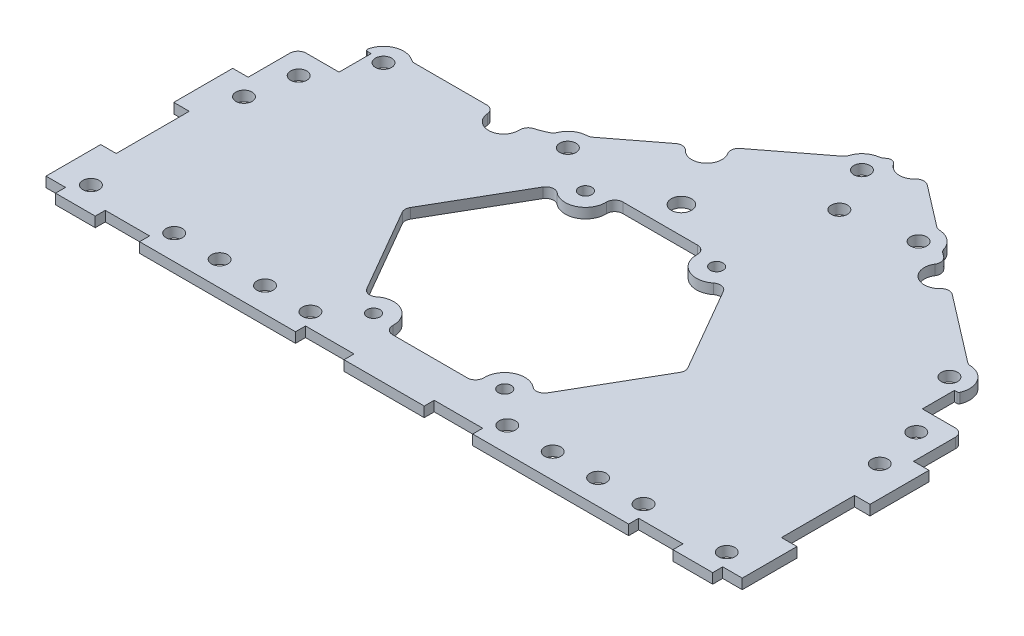
SolidWorks part; units mm, degrees
material "Alum Plate"
ref_plane "Front Plane" through (0, 0, 0) normal (0, 0, 1) x (1, 0, 0)
ref_plane "Top Plane" through (0, 0, 0) normal (0, 1, 0) x (1, 0, 0)
ref_plane "Right Plane" through (0, 0, 0) normal (1, 0, 0) x (0, 0, -1)
sketch "Top Layout" plane through (0, 0, 0) normal (0, 1, 0) x (1, 0, 0)
  line L0 (-114.046, -123.825) -> (-104.775, -123.825) construction
  line L1 (-104.775, -142.875) -> (-101.6, -142.875)
  line L2 (-104.775, -142.875) -> (-104.775, -104.775)
  line L3 (-104.775, -104.775) -> (-101.6, -104.775)
  line L4 (-101.6, -142.875) -> (-101.6, -104.775)
  line L5 (-104.775, -142.875) -> (-101.6, -104.775) construction
  line L6 (-104.775, -104.775) -> (-101.6, -142.875) construction
  line L7 (-19.05, -105.8164) -> (-101.6, -105.8164)
  line L8 (-19.05, -105.8164) -> (-19.05, -141.8336)
  line L9 (-19.05, -141.8336) -> (-101.6, -141.8336)
  line L10 (-101.6, -105.8164) -> (-101.6, -141.8336)
  line L11 (-19.05, -105.8164) -> (-101.6, -141.8336) construction
  line L12 (-19.05, -141.8336) -> (-101.6, -105.8164) construction
  line L13 (-133.096, -85.725) -> (-114.046, -85.725)
  line L14 (-133.096, -85.725) -> (-133.096, -161.925)
  line L15 (-133.096, -161.925) -> (-114.046, -161.925)
  line L16 (-114.046, -85.725) -> (-114.046, -161.925)
  line L17 (-133.096, -85.725) -> (-114.046, -161.925) construction
  line L18 (-133.096, -161.925) -> (-114.046, -85.725) construction
  line L19 (-104.775, -123.825) -> (0, -123.825) construction
  line L20 (0, -123.825) -> (0, 0) construction
  line L21 (-52.3528, -40.1717) -> (0, 0) construction
  line L22 (-70.6449, -16.3328) -> (-18.2922, 23.8388)
  line L23 (-34.0606, -64.0105) -> (18.2922, -23.8388)
  line L24 (-30.9251, 40.3023) -> (-122.2248, -29.7544)
  line L25 (-153.9748, -53.975) -> (-153.9748, -123.825)
  line L26 (-109.5248, -162.052) -> (109.5248, -162.052)
  line L27 (0, -162.052) -> (0, -123.825) construction
  line L28 (-109.5248, -162.052) -> (-109.5248, -20.0093) construction
  line L29 (-104.775, -142.875) -> (-104.775, -152.527)
  line L30 (-104.775, -152.527) -> (104.775, -152.527)
  line L31 (104.775, -104.775) -> (101.6, -104.775)
  line L32 (-144.4498, -73.025) -> (-109.5248, -73.025)
  line L33 (-144.4498, -73.025) -> (-144.4498, -123.825)
  line L34 (-144.4498, -123.825) -> (-109.5248, -123.825) construction
  line L35 (-109.5248, -73.025) -> (-109.5248, -162.052)
  line L36 (-144.4498, -73.025) -> (-109.5248, -123.825) construction
  line L37 (-144.4498, -123.825) -> (-109.5248, -73.025) construction
  line L38 (101.6, -142.875) -> (101.6, -104.775)
  line L39 (104.775, -142.875) -> (101.6, -142.875)
  line L40 (104.775, -142.875) -> (104.775, -104.775)
  line L41 (104.775, -142.875) -> (104.775, -152.527)
  line L42 (109.5248, -162.052) -> (109.5248, -20.0093) construction
  line L43 (30.9251, 40.3023) -> (122.2248, -29.7544)
  line L45 (19.05, -141.8336) -> (101.6, -141.8336)
  line L46 (101.6, -105.8164) -> (101.6, -141.8336)
  line L47 (19.05, -105.8164) -> (101.6, -105.8164)
  line L48 (19.05, -105.8164) -> (19.05, -141.8336)
  line L49 (133.096, -161.925) -> (114.046, -161.925)
  line L50 (114.046, -85.725) -> (114.046, -161.925)
  line L51 (133.096, -85.725) -> (114.046, -85.725)
  line L52 (133.096, -85.725) -> (133.096, -161.925)
  line L53 (144.4498, -123.825) -> (109.5248, -123.825) construction
  line L54 (109.5248, -73.025) -> (109.5248, -162.052)
  line L55 (144.4498, -73.025) -> (109.5248, -73.025)
  line L56 (144.4498, -73.025) -> (144.4498, -123.825)
  line L57 (-109.5248, -123.825) -> (-109.5248, -162.052) construction
  line L62 (-153.9748, -53.975) -> (-122.2248, -53.975)
  line L63 (-122.2248, -53.975) -> (-122.2248, -29.7544)
  line L64 (-144.4498, -123.825) -> (-153.9748, -123.825)
  line L65 (153.9748, -53.975) -> (153.9748, -123.825)
  line L66 (109.5248, -123.825) -> (109.5248, -162.052) construction
  line L67 (144.4498, -123.825) -> (153.9748, -123.825)
  line L68 (122.2248, -29.7544) -> (122.2248, -53.975)
  line L73 (-104.775, -104.775) -> (-104.775, -16.3647) construction
  line L74 (-95.25, -162.052) -> (-95.25, -9.0559) construction
  line L75 (-109.5248, -162.052) -> (-109.5248, -123.825) construction
  line L76 (109.5248, -162.052) -> (109.5248, -123.825) construction
  line L77 (122.2248, -53.975) -> (153.9748, -53.975)
  line L83 (104.775, -155.5496) -> (-104.775, -155.5496) construction
  line L88 (95.25, -162.052) -> (95.25, -9.0559) construction
  line L89 (104.775, -104.775) -> (104.775, -16.3647) construction
  line L92 (-104.775, -152.527) -> (-104.775, -162.052) construction
  line L93 (-14.605, -76.327) -> (14.605, -76.327)
  line L94 (-14.605, -76.327) -> (-14.605, -152.527)
  line L95 (-14.605, -152.527) -> (14.605, -152.527)
  line L96 (14.605, -76.327) -> (14.605, -152.527)
  line L97 (-14.605, -76.327) -> (14.605, -152.527) construction
  line L98 (-14.605, -152.527) -> (14.605, -76.327) construction
  line L99 (104.775, -152.527) -> (104.775, -162.052) construction
  line L100 (-19.05, -105.8164) -> (0, -105.8164) construction
  line L107 (0, -105.8164) -> (19.05, -105.8164) construction
  line L108 (104.775, -123.825) -> (114.046, -123.825) construction
  circle A0 centre (0, 0) radius 114.3
  circle A1 centre (0, 0) radius 6.35
  circle A2 centre (-52.3528, -40.1717) radius 17.8
  circle A3 centre (0, 0) radius 30.0482
  circle A4 centre (-52.3528, -40.1717) radius 30.0482
  arc A5 (-30.9251, 40.3023) -> (30.9251, 40.3023) centre (0, 0) cw
  point P2 (-103.1875, -123.825)
  point P7 (-60.325, -123.825)
  point P12 (-123.571, -123.825)
  point P30 (-126.9873, -98.425)
  point P35 (0, -114.427)
  point P53 (0, -152.527)
  dimension "D1" = 35.6
  dimension "D2" = 12.7
  dimension "D3" = 228.6
  dimension "D11" = 60.0964
  dimension "D12" = 50.8
  dimension "D14" = 52.5
  dimension "D4" = 3.175
  dimension "D5" = 19.05
  dimension "D6" = 76.2
  dimension "D7" = 82.55
  dimension "D8" = 38.1
  dimension "D9" = 104.775
  dimension "D10" = 18.0086
  dimension "D13" = 9.525
  dimension "D15" = 4.7498
  dimension "D16" = 9.525
  dimension "D17" = 9.652
  dimension "D18" = 50.8
  dimension "D19" = 12.446
  dimension "D20" = 65.9892
  dimension "D21" = 19.05
  dimension "D22" = 34.925
  dimension "D23" = 123.825
  dimension "D24" = 12.7
  dimension "D25" = 9.525
  dimension "D26" = 29.21
  dimension "D27" = 76.2
  dimension "D28" = 3.0226
sketch "Side Layout" plane through (0, 0, 0) normal (1, 0, 0) x (0, 0, -1)
  line L0 (0, -38.1) -> (0, 33.7344) construction
  line L1 (-114.3, -20.955) -> (114.3, -20.955)
  line L2 (-114.3, -20.955) -> (-114.3, -33.655)
  line L3 (-114.3, -33.655) -> (114.3, -33.655)
  line L4 (114.3, -20.955) -> (114.3, -33.655)
  line L5 (-114.3, -20.955) -> (114.3, -33.655) construction
  line L6 (-114.3, -33.655) -> (114.3, -20.955) construction
  line L7 (-9.525, -32.9406) -> (9.525, -32.9406)
  line L8 (-9.525, -32.9406) -> (-9.525, -38.1)
  line L9 (-9.525, -38.1) -> (9.525, -38.1)
  line L10 (9.525, -32.9406) -> (9.525, -38.1)
  line L11 (-9.525, -32.9406) -> (9.525, -38.1) construction
  line L12 (-9.525, -38.1) -> (9.525, -32.9406) construction
  line L13 (-11.9126, -29.3338) -> (11.9126, -29.3338)
  line L14 (-11.9126, -29.3338) -> (-11.9126, -32.9406)
  line L15 (-11.9126, -32.9406) -> (11.9126, -32.9406)
  line L16 (11.9126, -29.3338) -> (11.9126, -32.9406)
  line L17 (-11.9126, -29.3338) -> (11.9126, -32.9406) construction
  line L18 (-11.9126, -32.9406) -> (11.9126, -29.3338) construction
  line L19 (-6.35, -32.9406) -> (6.35, -32.9406)
  line L20 (-6.35, -32.9406) -> (-6.35, 33.7344)
  line L21 (-6.35, 33.7344) -> (6.35, 33.7344)
  line L22 (6.35, -32.9406) -> (6.35, 33.7344)
  line L23 (-6.35, -32.9406) -> (6.35, 33.7344) construction
  line L24 (-6.35, 33.7344) -> (6.35, -32.9406) construction
  line L25 (-162.052, 0) -> (-123.825, 0) construction
  line L26 (114.3, -33.655) -> (114.3, 0) construction
  line L27 (-142.875, 19.05) -> (-104.775, 19.05)
  line L28 (-40.1717, -9.525) -> (-40.1717, 5.4) construction
  line L29 (-142.875, 19.05) -> (-142.875, -19.05)
  line L30 (-142.875, -19.05) -> (-104.775, -19.05)
  line L31 (-104.775, 19.05) -> (-104.775, -19.05)
  line L32 (-142.875, 19.05) -> (-104.775, -19.05) construction
  line L33 (-142.875, -19.05) -> (-104.775, 19.05) construction
  line L34 (-130.175, -38.1) -> (-117.9516, -38.1) construction
  line L35 (-57.9717, -14.6) -> (-22.3717, -14.6)
  line L36 (-30.0482, -2.794) -> (30.0482, -2.794)
  line L37 (-30.0482, -2.794) -> (-30.0482, -20.955)
  line L38 (-30.0482, -20.955) -> (30.0482, -20.955)
  line L39 (30.0482, -2.794) -> (30.0482, -20.955)
  line L40 (-30.0482, -2.794) -> (30.0482, -20.955) construction
  line L41 (-30.0482, -20.955) -> (30.0482, -2.794) construction
  line L42 (-30.0482, -2.794) -> (-30.0482, 0) construction
  line L43 (-123.825, 0) -> (0, 0) construction
  line L44 (-57.9717, -14.6) -> (-57.9717, 25.4)
  line L45 (-57.9717, 25.4) -> (-22.3717, 25.4)
  line L46 (-22.3717, -14.6) -> (-22.3717, 25.4)
  line L47 (-19.05, 0) -> (19.05, 0)
  line L48 (-19.05, 0) -> (-19.05, -1.9812)
  line L49 (-19.05, -1.9812) -> (19.05, -1.9812)
  line L50 (19.05, 0) -> (19.05, -1.9812)
  line L51 (-19.05, 0) -> (19.05, -1.9812) construction
  line L52 (-19.05, -1.9812) -> (19.05, 0) construction
  line L53 (-70.2199, -3.175) -> (-10.1235, -3.175)
  line L54 (-70.2199, -3.175) -> (-70.2199, -15.875)
  line L55 (-70.2199, -15.875) -> (-10.1235, -15.875)
  line L56 (-10.1235, -3.175) -> (-10.1235, -15.875)
  line L57 (-70.2199, -3.175) -> (-10.1235, -15.875) construction
  line L58 (-70.2199, -15.875) -> (-10.1235, -3.175) construction
  line L59 (-40.1717, -9.525) -> (-40.1717, 0) construction
  line L60 (-57.9717, -14.6) -> (-22.3717, 25.4) construction
  line L61 (-57.9717, 25.4) -> (-22.3717, -14.6) construction
  line L62 (-22.3717, 0) -> (-57.9717, 0) construction
  line L63 (-137.8162, 0) -> (-123.825, -13.9912) construction
  line L64 (-139.065, 15.24) -> (-108.585, 15.24) construction
  line L65 (-139.065, 15.24) -> (-139.065, -15.24) construction
  line L66 (-139.065, -15.24) -> (-108.585, -15.24) construction
  line L67 (-108.585, 15.24) -> (-108.585, -15.24) construction
  line L68 (-139.065, 15.24) -> (-108.585, -15.24) construction
  line L69 (-139.065, -15.24) -> (-108.585, 15.24) construction
  line L70 (-137.8162, 0) -> (-123.825, 13.9912) construction
  line L71 (-123.825, -13.9912) -> (-109.8338, 0) construction
  line L72 (-123.825, 13.9912) -> (-109.8338, 0) construction
  line L73 (-137.8162, 0) -> (-109.8338, 0) construction
  line L74 (-123.825, -13.9912) -> (-123.825, 13.9912) construction
  line L75 (-6.35, 17.8594) -> (6.35, 17.8594)
  line L76 (114.3, 0) -> (-114.3, 0) construction
  line L77 (-22.3717, 19.05) -> (-6.35, 19.05) construction
  line L78 (-123.825, 38.1) -> (-97.9206, 38.1) construction
  line L79 (-19.05, -3.5814) -> (19.05, -3.5814)
  line L80 (-19.05, -3.5814) -> (-19.05, -1.9812)
  line L81 (-19.05, -1.9812) -> (19.05, -1.9812)
  line L82 (19.05, -3.5814) -> (19.05, -1.9812)
  line L83 (-19.05, -3.5814) -> (19.05, -1.9812) construction
  line L84 (-19.05, -1.9812) -> (19.05, -3.5814) construction
  line L85 (-8.7376, -16.7608) -> (8.7376, -16.7608)
  line L86 (-8.7376, -16.7608) -> (-8.7376, -29.3338)
  line L87 (-8.7376, -29.3338) -> (8.7376, -29.3338)
  line L88 (8.7376, -16.7608) -> (8.7376, -29.3338)
  line L89 (-8.7376, -16.7608) -> (8.7376, -29.3338) construction
  line L90 (-8.7376, -29.3338) -> (8.7376, -16.7608) construction
  line L91 (-8.7376, -3.5814) -> (8.7376, -3.5814)
  line L92 (-8.7376, -3.5814) -> (-8.7376, -16.1544)
  line L93 (-8.7376, -16.1544) -> (8.7376, -16.1544)
  line L94 (8.7376, -3.5814) -> (8.7376, -16.1544)
  line L95 (-8.7376, -3.5814) -> (8.7376, -16.1544) construction
  line L96 (-8.7376, -16.1544) -> (8.7376, -3.5814) construction
  circle A0 centre (-123.825, 0) radius 18.0086
  circle A1 centre (-123.825, 0) radius 38.1
  circle A2 centre (-139.065, 15.24) radius 1.905
  circle A3 centre (-108.585, 15.24) radius 1.905
  circle A4 centre (-108.585, -15.24) radius 1.905
  circle A5 centre (-139.065, -15.24) radius 1.905
  circle A6 centre (-137.8162, 0) radius 1.6002
  circle A7 centre (-123.825, 13.9912) radius 1.6002
  circle A8 centre (-109.8338, 0) radius 1.6002
  circle A9 centre (-123.825, -13.9912) radius 1.6002
  point P0 (0, -27.305)
  point P6 (0, -31.1372)
  point P7 (0, -35.5203)
  point P21 (0, 0.3969)
  point P32 (0, -11.8745)
  point P43 (0, -0.9906)
  point P55 (-40.1717, -9.525)
  point P72 (-40.1717, 5.4)
  point P88 (0, -23.0473)
  point P93 (0, -2.7813)
  point P102 (0, -9.8679)
  dimension "D17" = 3.81
  dimension "D18" = 3.2004
  dimension "D1" = 12.7
  dimension "D2" = 5.1594
  dimension "D3" = 19.05
  dimension "D4" = 3.6068
  dimension "D5" = 23.8252
  dimension "D6" = 12.7
  dimension "D7" = 18.161
  dimension "D8" = 1.9812
  dimension "D9" = 12.7
  dimension "D10" = 40
  dimension "D11" = 25.4
  dimension "D12" = 50.8
  dimension "D13" = 41.275
  dimension "D14" = 30.48
  dimension "D15" = 4.445
  dimension "D16" = 19.7866
  dimension "D19" = 15.875
  dimension "D20" = 6.35
  dimension "D21" = 38.1
  dimension "D22" = 1.6002
  dimension "D23" = 38.1
  dimension "D24" = 17.4752
  dimension "D25" = 12.573
ref_plane "Plane1" through (0, 25.4, 0) normal (0, 1, 0) x (1, 0, 0)
sketch "Sketch3" plane through (0, 25.4, 0) normal (0, 1, 0) x (1, 0, 0)
  line L0 (-104.775, -36.3747) -> (-30.9251, 20.2924)
  line L1 (-104.775, -104.775) -> (-104.775, -16.3647) construction
  line L2 (0, -200130.175) -> (0, 199882.0484) construction
  line L3 (-30.9251, 40.3023) -> (-122.2248, -29.7544) construction
  line L5 (-104.775, -36.3747) -> (-104.775, -77.6497)
  line L6 (-92.075, -77.6497) -> (-104.775, -77.6497)
  line L7 (30.9251, 20.2924) -> (104.775, -36.3747)
  line L8 (104.775, -77.6497) -> (92.075, -77.6497)
  line L9 (104.775, -36.3747) -> (104.775, -77.6497)
  line L11 (104.775, -104.775) -> (104.775, -16.3647) construction
  line L12 (30.9251, 40.3023) -> (122.2248, -29.7544) construction
  line L13 (92.075, -74.6536) -> (24.1423, -22.5271)
  line L14 (-32.2514, -66.3682) -> (20.1013, -26.1965)
  line L15 (-30.9251, 20.2924) -> (0, 44.022)
  line L16 (0, 44.022) -> (30.9251, 20.2924)
  line L17 (-92.075, -77.6497) -> (-92.075, -73.1917)
  line L19 (-92.075, -73.1917) -> (-52.3528, -73.1917)
  line L20 (92.075, -74.6536) -> (92.075, -77.6497)
  circle A0 centre (-52.3528, -40.1717) radius 17.8 construction
  circle A1 centre (-52.3528, -40.1717) radius 17.8
  circle A2 centre (0, 0) radius 6.35
  circle A3 centre (0, 0) radius 6.35 construction
  arc A4 (-52.3528, -73.1917) -> (-32.2514, -66.3682) centre (-52.3528, -40.1717) ccw
  arc A5 (20.1013, -26.1965) -> (24.1423, -22.5271) centre (0, 0) ccw
  arc A6 (30.9251, 20.2924) -> (-30.9251, 20.2924) centre (0, -20.01) ccw construction
  point P28 (0, 44.022)
  dimension "D1" = 33.02
  dimension "D5" = 50.8
  dimension "D2" = 41.275
  dimension "D3" = 34.925
  dimension "D4" = 12.7
  dimension "D6" = 38.1
ref_plane "Plane3" through (-104.775, 0, 0) normal (-1, 0, 0) x (0, 0, 1)
sketch "Sketch6" plane through (-104.775, 0, 0) normal (-1, 0, 0) x (0, 0, 1)
  line L0 (162.052, -25.4) -> (162.052, 25.4)
  line L1 (162.052, 25.4) -> (77.6497, 25.4)
  line L2 (36.3747, 25.4) -> (77.6497, 25.4) construction
  line L3 (147.7645, 11.1125) -> (162.052, 11.1125) construction
  line L4 (162.052, 0) -> (71.2997, 0) construction
  line L5 (77.6497, 25.4) -> (77.6497, 19.05)
  line L6 (77.6497, 19.05) -> (36.3747, 19.05)
  line L7 (36.3747, 19.05) -> (36.3747, 6.35)
  line L8 (36.3747, 6.35) -> (71.2997, 6.35)
  line L10 (99.6315, -3.175) -> (99.6315, 11.1125) construction
  line L11 (71.2997, -25.4) -> (162.052, -25.4)
  line L13 (71.2997, 6.35) -> (71.2997, -25.4)
  line L14 (152.527, -25.4) -> (152.527, 25.4) construction
  line L15 (99.6315, 11.1125) -> (99.6315, 25.4) construction
  line L16 (147.7645, 11.1125) -> (147.7645, 25.4) construction
  line L17 (94.869, -7.9375) -> (104.394, -7.9375) construction
  line L18 (94.869, -7.9375) -> (94.869, 25.4) construction
  line L19 (94.869, 25.4) -> (104.394, 25.4) construction
  line L20 (104.394, -7.9375) -> (104.394, 25.4) construction
  line L21 (94.869, -7.9375) -> (104.394, 25.4) construction
  line L22 (94.869, 25.4) -> (104.394, -7.9375) construction
  line L23 (147.7645, 11.1125) -> (147.7645, -3.175) construction
  line L24 (104.394, -7.9375) -> (123.825, -7.9375) construction
  line L25 (143.002, -7.9375) -> (152.527, -7.9375) construction
  line L26 (143.002, -7.9375) -> (143.002, 25.4) construction
  line L27 (143.002, 25.4) -> (152.527, 25.4) construction
  line L28 (152.527, -7.9375) -> (152.527, 25.4) construction
  line L29 (143.002, -7.9375) -> (152.527, 25.4) construction
  line L30 (143.002, 25.4) -> (152.527, -7.9375) construction
  line L31 (123.825, -7.9375) -> (152.527, -7.9375) construction
  line L32 (104.775, 19.05) -> (104.775, -19.05) construction
  line L34 (155.702, -25.4) -> (155.702, 25.4) construction
  circle A0 centre (109.8338, 0) radius 1.6002 construction
  circle A1 centre (123.825, 13.9912) radius 1.6002 construction
  circle A2 centre (137.8162, 0) radius 1.6002 construction
  circle A3 centre (123.825, -13.9912) radius 1.6002 construction
  circle A4 centre (109.8338, 0) radius 1.6002 construction
  circle A5 centre (123.825, 13.9912) radius 1.6002 construction
  circle A6 centre (137.8162, 0) radius 1.6002 construction
  circle A7 centre (123.825, -13.9912) radius 1.6002 construction
  circle A8 centre (123.825, 0) radius 18.0086 construction
  circle A9 centre (123.825, 0) radius 18.0086 construction
  circle A10 centre (123.825, 0) radius 9.525
  circle A11 centre (108.585, -15.24) radius 1.905 construction
  circle A12 centre (108.585, 15.24) radius 1.905 construction
  circle A13 centre (139.065, 15.24) radius 1.905 construction
  circle A14 centre (139.065, -15.24) radius 1.905 construction
  circle A15 centre (108.585, -15.24) radius 1.905
  circle A16 centre (108.585, 15.24) radius 1.905
  circle A17 centre (139.065, 15.24) radius 1.905
  circle A18 centre (139.065, -15.24) radius 1.905
  circle A19 centre (147.7645, 11.1125) radius 2.5527
  circle A26 centre (99.6315, 11.1125) radius 2.5527
  circle A27 centre (99.6315, -3.175) radius 2.5527
  circle A28 centre (147.7645, -3.175) radius 2.5527
  point P29 (0, 0)
  point P55 (99.6315, 8.7312)
  point P61 (147.7645, 8.7312)
  dimension "D4" = 19.05
  dimension "D7" = 5.1054
  dimension "D1" = 6.35
  dimension "D2" = 12.7
  dimension "D3" = 25.4
  dimension "D5" = 6.35
  dimension "D6" = 3.175
  dimension "D8" = 0.381
  dimension "D9" = 14.2875
  dimension "D10" = 9.525
  dimension "D12" = 33.3375
ref_plane "Plane4" through (0, 19.05, 0) normal (0, 1, 0) x (1, 0, 0)
sketch "Sketch12" plane through (0, 19.05, 0) normal (0, 1, 0) x (1, 0, 0)
  line L0 (-104.775, -77.6497) -> (-104.775, -36.3747)
  line L1 (-104.775, -36.3747) -> (-92.075, -36.3747)
  line L3 (-92.075, -36.3747) -> (-92.075, -77.6497)
  line L5 (-92.075, -77.6497) -> (-104.775, -77.6497)
  line L6 (-98.425, -77.6497) -> (-98.425, -63.3622) construction
  line L7 (-98.425, -63.3622) -> (-98.425, -50.6622) construction
  line L8 (-98.425, -50.6622) -> (-98.425, -36.3747) construction
  line L10 (-98.425, -36.3747) -> (-104.775, -36.3747) construction
  circle A0 centre (-98.425, -63.3622) radius 2.5527
  circle A1 centre (-98.425, -50.6622) radius 2.5527
  dimension "D2" = 5.1054
  dimension "D1" = 12.7
  dimension "D3" = 12.7
sketch "Sketch25" plane through (0, 25.4, 0) normal (0, 1, 0) x (1, 0, 0)
  line L0 (-104.775, -152.527) -> (104.775, -152.527)
  line L1 (-104.775, -152.527) -> (104.775, -152.527) construction
  line L2 (104.775, -152.527) -> (104.775, -162.052)
  line L3 (104.775, -162.052) -> (-104.775, -162.052)
  line L4 (-104.775, -162.052) -> (-104.775, -152.527)
ref_plane "Plane5" through (0, 0, 152.527) normal (0, 0, 1) x (1, 0, 0)
sketch "Sketch41" plane through (0, 0, 152.527) normal (0, 0, 1) x (1, 0, 0)
  line L0 (-104.775, -7.9375) -> (-104.775, 25.4) construction
  line L1 (-104.775, -7.9375) -> (-104.775, 12.7)
  line L2 (-104.775, -7.9375) -> (104.775, -7.9375)
  line L3 (104.775, -7.9375) -> (104.775, 12.7)
  line L4 (104.775, 25.4) -> (-104.775, 25.4)
  line L5 (0, -7.9375) -> (0, 25.4) construction
  line L6 (-104.775, 3.9624) -> (-100.0125, 3.9624) construction
  line L7 (-100.0125, 3.9624) -> (-100.0125, 25.4) construction
  line L8 (104.775, 3.9624) -> (100.0125, 3.9624) construction
  line L9 (100.0125, 3.9624) -> (100.0125, 25.4) construction
  line L10 (19.05, 20.6375) -> (23.8252, 20.6375) construction
  line L11 (19.05, 15.875) -> (78.5876, 15.875) construction
  line L12 (19.05, 15.875) -> (19.05, 25.4) construction
  line L13 (19.05, 25.4) -> (78.5876, 25.4) construction
  line L14 (78.5876, 15.875) -> (78.5876, 25.4) construction
  line L15 (19.05, 15.875) -> (78.5876, 25.4) construction
  line L16 (19.05, 25.4) -> (78.5876, 15.875) construction
  line L17 (23.8252, 20.6375) -> (38.1127, 20.6375) construction
  line L18 (38.1127, 20.6375) -> (52.4002, 20.6375) construction
  line L19 (52.4002, 20.6375) -> (66.6877, 20.6375) construction
  line L20 (-104.775, 25.4) -> (-112.395, 25.4)
  line L21 (-112.395, 25.4) -> (-112.395, 3.175)
  line L22 (-112.395, 3.175) -> (-109.5248, 3.175)
  line L23 (-109.5248, 3.175) -> (-109.5248, 12.7)
  line L24 (-109.5248, 12.7) -> (-104.775, 12.7)
  line L25 (-104.775, 12.7) -> (-104.775, 25.4) construction
  line L26 (104.775, 25.4) -> (112.395, 25.4)
  line L27 (112.395, 25.4) -> (112.395, 3.175)
  line L28 (112.395, 3.175) -> (109.5248, 3.175)
  line L29 (109.5248, 3.175) -> (109.5248, 12.7)
  line L30 (109.5248, 12.7) -> (104.775, 12.7)
  line L31 (104.775, 12.7) -> (104.775, 25.4) construction
  line L32 (-100.0125, 3.9624) -> (-87.3125, 3.9624) construction
  line L33 (-63.5, -1.5875) -> (0, -1.5875) construction
  line L34 (0, -1.5875) -> (63.5, -1.5875) construction
  line L35 (63.5, -1.5875) -> (63.5, -7.9375) construction
  circle A0 centre (-100.0125, 3.9624) radius 2.5527
  circle A1 centre (100.0125, 3.9624) radius 2.5527
  circle A2 centre (23.8252, 20.6375) radius 2.5527
  circle A3 centre (38.1127, 20.6375) radius 2.5527
  circle A4 centre (52.4002, 20.6375) radius 2.5527
  circle A5 centre (66.6877, 20.6375) radius 2.5527
  circle A6 centre (-66.6877, 20.6375) radius 2.5527
  circle A7 centre (-52.4002, 20.6375) radius 2.5527
  circle A8 centre (-38.1127, 20.6375) radius 2.5527
  circle A9 centre (-23.8252, 20.6375) radius 2.5527
  circle A10 centre (-87.3125, 3.9624) radius 2.5527
  circle A11 centre (87.3125, 3.9624) radius 2.5527
  circle A12 centre (-63.5, -1.5875) radius 2.5527
  circle A13 centre (63.5, -1.5875) radius 2.5527
  point P14 (48.8188, 20.6375)
  dimension "D3" = 5.1054
  dimension "D7" = 5.1054
  dimension "D1" = 21.4376
  dimension "D2" = 4.7625
  dimension "D4" = 9.525
  dimension "D5" = 59.5376
  dimension "D6" = 4.7752
  dimension "D8" = 14.2875
  dimension "D9" = 7.62
  dimension "D10" = 4.7498
  dimension "D11" = 12.7
  dimension "D12" = 9.525
  dimension "D13" = 19.05
  dimension "D14" = 12.7
  dimension "D15" = 6.35
  dimension "D16" = 63.5
sketch "Sketch44" plane through (0, 25.4, 0) normal (0, 1, 0) x (1, 0, 0)
  line L0 (73.8315, -147.7645) -> (73.8315, -152.527) construction
  line L1 (92.075, -74.6536) -> (92.075, -77.6497) construction
  line L2 (-92.075, -77.6497) -> (-92.075, -73.1917) construction
  line L3 (0, -123.825) -> (0, 0) construction
  line L4 (-92.075, -73.1917) -> (-52.3528, -73.1917) construction
  line L5 (-104.775, -104.775) -> (-104.775, -16.3647) construction
  line L6 (-32.2514, -66.3682) -> (20.1013, -26.1965) construction
  line L21 (-104.775, -68.1247) -> (-104.775, -152.527)
  line L22 (-104.775, -152.527) -> (104.775, -152.527)
  line L23 (104.775, -152.527) -> (104.775, -68.1247)
  line L34 (-104.775, -99.6315) -> (-100.0125, -99.6315) construction
  line L35 (-104.775, -147.7645) -> (-100.0125, -147.7645) construction
  line L36 (0, -152.527) -> (0, -35.6178) construction
  line L38 (30.969, -147.7645) -> (45.2565, -147.7645) construction
  line L39 (45.2565, -147.7645) -> (59.544, -147.7645) construction
  line L40 (59.544, -147.7645) -> (73.8315, -147.7645) construction
  line L41 (23.8252, -152.527) -> (30.969, -152.527) construction
  line L42 (104.775, -152.527) -> (-104.775, -152.527) construction
  line L43 (30.969, -152.527) -> (38.1127, -152.527) construction
  line L44 (30.969, -152.527) -> (30.969, -147.7645) construction
  line L45 (-92.075, -77.6497) -> (-104.775, -77.6497) construction
  line L48 (-35.1507, -62.5899) -> (-8.9743, -42.504) construction
  line L49 (-8.9743, -42.504) -> (17.2021, -22.4182) construction
  line L50 (45.5313, -32.9364) -> (87.3125, -64.9962) construction
  line L51 (92.075, -74.6536) -> (24.1423, -22.5271) construction
  line L52 (104.775, -77.6497) -> (92.075, -77.6497) construction
  line L79 (-104.775, -68.1247) -> (-92.075, -68.1247)
  line L80 (-92.075, -68.1247) -> (-92.075, -63.6667)
  line L85 (21.8118, -8.7328) -> (92.075, -62.6476)
  line L86 (-38.0499, -58.8115) -> (14.3028, -18.6398)
  line L87 (-92.075, -63.6667) -> (-52.3528, -63.6667)
  line L88 (92.075, -62.6476) -> (92.075, -68.1247)
  line L89 (92.075, -68.1247) -> (104.775, -68.1247)
  circle A0 centre (-73.8315, -147.7645) radius 2.5527
  circle A1 centre (-59.544, -147.7645) radius 2.5527
  circle A2 centre (-45.2565, -147.7645) radius 2.5527
  circle A3 centre (-30.969, -147.7645) radius 2.5527
  circle A17 centre (-100.0125, -99.6315) radius 2.5527
  circle A18 centre (-100.0125, -147.7645) radius 2.5527
  circle A19 centre (100.0125, -147.7645) radius 2.5527
  circle A20 centre (100.0125, -99.6315) radius 2.5527
  circle A21 centre (30.969, -147.7645) radius 2.5527
  circle A22 centre (45.2565, -147.7645) radius 2.5527
  circle A23 centre (59.544, -147.7645) radius 2.5527
  circle A24 centre (73.8315, -147.7645) radius 2.5527
  circle A25 centre (-87.3125, -68.4292) radius 4.7625 construction
  circle A26 centre (-35.1507, -62.5899) radius 4.7625 construction
  circle A27 centre (-8.9743, -42.504) radius 4.7625 construction
  circle A28 centre (17.2021, -22.4182) radius 4.7625 construction
  circle A29 centre (45.5313, -32.9364) radius 4.7625 construction
  circle A30 centre (87.3125, -64.9962) radius 4.7625 construction
  circle A32 centre (-87.3125, -68.4292) radius 2.5527
  circle A33 centre (-35.1507, -62.5899) radius 2.5527
  circle A34 centre (-8.9743, -42.504) radius 2.5527 construction
  circle A35 centre (17.2021, -22.4182) radius 2.5527
  circle A36 centre (45.5313, -32.9364) radius 2.5527
  circle A37 centre (87.3125, -64.9962) radius 2.5527
  circle A38 centre (-97.155, -85.2697) radius 7.62 construction
  circle A39 centre (97.155, -85.2697) radius 7.62 construction
  circle A40 centre (24.4294, -36.7543) radius 11.1125 construction
  arc A41 (20.1013, -26.1965) -> (24.1423, -22.5271) centre (0, 0) ccw construction
  circle A42 centre (-97.155, -85.2697) radius 2.5527
  circle A43 centre (24.4294, -36.7543) radius 2.5527
  circle A44 centre (97.155, -85.2697) radius 2.5527
  arc A56 (14.3028, -18.6398) -> (21.8118, -8.7328) centre (0, 0) ccw
  arc A57 (-52.3528, -63.6667) -> (-38.0499, -58.8115) centre (-52.3528, -40.1717) ccw
  point P4 (-104.775, -152.527)
  dimension "D2" = 5.1054
  dimension "D7" = 5.1054
  dimension "D8" = 15.24
  dimension "D3" = 9.525
  dimension "D9" = 9.525
  dimension "D11" = 22.225
  dimension "D4" = 4.7625
  dimension "D5" = 14.2875
  dimension "D6" = 9.525
  dimension "D1" = 4.7625
  dimension "D10" = 52.664
extrude "Top Plate Extrude-----------" add sketch "Sketch44" along normal blind 3.175
sketch "Sketch82" plane through (0, 28.575, 0) normal (0, 1, 0) x (1, 0, 0)
  line L0 (-52.3528, -63.6667) -> (-92.075, -63.6667) construction
  line L1 (-52.3528, -65.5717) -> (-52.3528, -63.6667) construction
  line L2 (-12.4467, -41.5667) -> (-13.6064, -40.0553) construction
  line L3 (14.3028, -18.6398) -> (-38.0499, -58.8115) construction
  line L4 (24.5175, -13.2101) -> (25.6772, -11.6988) construction
  line L5 (92.075, -62.6476) -> (21.8118, -8.7328) construction
  line L6 (58.2962, -39.1295) -> (59.4559, -37.6181) construction
  line L7 (21.4643, -9.5551) -> (21.8118, -8.7328)
  line L8 (21.8118, -8.7328) -> (22.2143, -9.0416)
  circle A0 centre (-52.3528, -65.5717) radius 4.7625
  circle A1 centre (-12.4467, -41.5667) radius 4.7625
  arc A2 (21.4643, -9.5551) -> (22.2143, -9.0416) centre (24.5175, -13.2101) ccw
  circle A3 centre (58.2962, -39.1295) radius 4.7625
  arc A4 (14.3028, -18.6398) -> (21.8118, -8.7328) centre (0, 0) ccw construction
  dimension "D1" = 9.525
  dimension "D2" = 1.905
  dimension "D3" = 30.8104
  dimension "D4" = 83.6926
  dimension "D5" = 41.1154
extrude "Cut-Extrude38" cut sketch "Sketch82" against normal up to surface (3.175 mm away) up to face at (-4.435, 25.4, 71.2837)
sketch "Sketch72" plane through (0, 25.4, 0) normal (0, 1, 0) x (1, 0, 0)
  line L0 (-104.775, -68.1247) -> (-104.775, -152.527) construction
  line L1 (-104.775, -152.527) -> (-109.5248, -152.527)
  line L2 (-104.775, -152.527) -> (-104.775, -135.0645)
  line L3 (-104.775, -135.0645) -> (-109.5248, -135.0645)
  line L4 (-109.5248, -152.527) -> (-109.5248, -135.0645)
  line L5 (-104.775, -152.527) -> (-109.5248, -135.0645) construction
  line L6 (-104.775, -135.0645) -> (-109.5248, -152.527) construction
  line L7 (-104.775, -152.527) -> (104.775, -152.527) construction
  line L8 (-77.0065, -152.527) -> (-73.8315, -147.7645) construction
  line L9 (-77.0065, -152.527) -> (-27.794, -152.527)
  line L10 (-77.0065, -152.527) -> (-77.0065, -155.5496)
  line L11 (-77.0065, -155.5496) -> (-27.794, -155.5496)
  line L12 (-27.794, -152.527) -> (-27.794, -155.5496)
  line L13 (-77.0065, -152.527) -> (-27.794, -155.5496) construction
  line L14 (-77.0065, -155.5496) -> (-27.794, -152.527) construction
  line L15 (-27.794, -152.527) -> (-30.969, -147.7645) construction
  line L16 (-77.0065, -152.527) -> (-77.0065, -147.7645) construction
  line L18 (-104.775, -93.5247) -> (-109.5248, -93.5247)
  line L19 (-104.775, -93.5247) -> (-104.775, -112.3315)
  line L20 (-104.775, -112.3315) -> (-109.5248, -112.3315)
  line L21 (-109.5248, -93.5247) -> (-109.5248, -112.3315)
  line L22 (-104.775, -93.5247) -> (-109.5248, -112.3315) construction
  line L23 (-104.775, -112.3315) -> (-109.5248, -93.5247) construction
  line L24 (0, -152.527) -> (-12.7, -152.527)
  line L25 (0, -152.527) -> (0, -155.5496)
  line L26 (0, -155.5496) -> (-12.7, -155.5496)
  line L27 (-12.7, -152.527) -> (-12.7, -155.5496)
  line L28 (0, -152.527) -> (-12.7, -155.5496) construction
  line L29 (0, -155.5496) -> (-12.7, -152.527) construction
  line L30 (-104.775, -68.1247) -> (-109.5248, -68.1247)
  line L31 (-104.775, -68.1247) -> (-104.775, -77.6497)
  line L32 (-104.775, -77.6497) -> (-109.5248, -77.6497)
  line L33 (-109.5248, -68.1247) -> (-109.5248, -77.6497)
  line L34 (-104.775, -68.1247) -> (-109.5248, -77.6497) construction
  line L35 (-104.775, -77.6497) -> (-109.5248, -68.1247) construction
  line L38 (-103.505, -155.5496) -> (-90.805, -155.5496)
  line L39 (-90.805, -152.527) -> (-90.805, -155.5496)
  line L40 (-103.505, -155.5496) -> (-103.505, -152.527)
  line L41 (-103.505, -155.5496) -> (-90.805, -152.527) construction
  line L42 (-103.505, -152.527) -> (-90.805, -152.527)
  line L43 (-77.0065, -147.7645) -> (-73.8315, -147.7645) construction
  line L44 (-103.505, -152.527) -> (-101.5221, -149.823) construction
  circle A0 centre (-100.0125, -147.7645) radius 2.5527 construction
  circle A1 centre (-73.8315, -147.7645) radius 2.5527 construction
  circle A2 centre (-30.969, -147.7645) radius 2.5527 construction
  point P4 (-107.1499, -143.7958)
  point P5 (-100.0125, -147.7645)
  point P16 (-52.4002, -154.0383)
  point P18 (-97.155, -154.0383)
  point P25 (-107.1499, -102.9281)
  point P34 (-6.35, -154.0383)
  point P39 (-107.1499, -72.8872)
  dimension "D1" = 4.7498
  dimension "D2" = 12.7
  dimension "D3" = 12.7
  dimension "D4" = 12.7
  dimension "D5" = 9.525
  dimension "D6" = 15.875
  dimension "D7" = 12.7
  dimension "D8" = 3.175
  dimension "D9" = 1.27
  dimension "D10" = 3.0226
extrude "Boss-Extrude27" add sketch "Sketch72" along normal through all
mirror "Mirror22" about plane through (0, 0, 0) normal (1, 0, 0) of "Boss-Extrude27"
sketch "Sketch86" plane through (0, 28.575, 0) normal (0, 1, 0) x (1, 0, 0)
  circle A0 centre (87.3125, -64.9962) radius 6.35
  circle A3 centre (17.2021, -22.4182) radius 6.35
  circle A4 centre (45.5313, -32.9364) radius 6.35
  circle A5 centre (-35.1507, -62.5899) radius 6.35
  circle A6 centre (-87.3125, -68.4292) radius 6.35
  circle A7 centre (87.3125, -64.9962) radius 2.5527 construction
  circle A8 centre (45.5313, -32.9364) radius 2.5527 construction
  circle A9 centre (17.2021, -22.4182) radius 2.5527 construction
  circle A10 centre (-35.1507, -62.5899) radius 2.5527 construction
  circle A11 centre (-87.3125, -68.4292) radius 2.5527 construction
  circle A12 centre (87.3125, -64.9962) radius 2.5527
  circle A13 centre (45.5313, -32.9364) radius 2.5527
  circle A14 centre (17.2021, -22.4182) radius 2.5527
  circle A15 centre (-35.1507, -62.5899) radius 2.5527
  circle A16 centre (-87.3125, -68.4292) radius 2.5527
  dimension "D1" = 12.7
extrude "Boss-Extrude31" add sketch "Sketch86" against normal through all
ref_plane "Plane8" through (0, 28.829, 0) normal (0, 1, 0) x (1, 0, 0)
sketch "Sketch87" plane through (0, 28.829, 0) normal (0, 1, 0) x (1, 0, 0)
  line L0 (0, -123.825) -> (0, 0) construction
  line L1 (-25.4, -66.802) -> (25.4, -66.802)
  line L2 (-25.4, -66.802) -> (-25.4, -143.002) construction
  line L3 (-25.4, -143.002) -> (25.4, -143.002)
  line L4 (25.4, -66.802) -> (25.4, -143.002) construction
  line L5 (-25.4, -66.802) -> (25.4, -143.002) construction
  line L6 (-25.4, -143.002) -> (25.4, -66.802) construction
  line L7 (-104.775, -152.527) -> (104.775, -152.527) construction
  line L8 (-25.4, -71.5645) -> (-20.6375, -71.5645) construction
  line L9 (-20.6375, -71.5645) -> (-20.6375, -66.802) construction
  line L10 (20.6375, -66.802) -> (20.6375, -71.5645) construction
  line L11 (20.6375, -71.5645) -> (25.4, -71.5645) construction
  line L12 (20.6375, -143.002) -> (20.6375, -138.2395) construction
  line L13 (20.6375, -138.2395) -> (25.4, -138.2395) construction
  line L14 (-20.6375, -143.002) -> (-20.6375, -138.2395) construction
  line L15 (-20.6375, -138.2395) -> (-25.4, -138.2395) construction
  line L16 (-25.4, -143.002) -> (-47.397, -104.902)
  line L17 (-47.397, -104.902) -> (-25.4, -66.802)
  line L18 (25.4, -66.802) -> (47.397, -104.902)
  line L19 (47.397, -104.902) -> (25.4, -143.002)
  circle A0 centre (-20.6375, -71.5645) radius 2.5527
  circle A1 centre (20.6375, -71.5645) radius 2.5527
  circle A3 centre (-20.6375, -138.2395) radius 2.5527
  circle A4 centre (20.6375, -138.2395) radius 2.5527
  point P0 (0, -104.902)
  dimension "D5" = 5.1054
  dimension "D1" = 50.8
  dimension "D2" = 9.525
  dimension "D3" = 76.2
  dimension "D4" = 4.7625
  dimension "D6" = 120
sketch "Sketch111" plane through (0, 28.575, 0) normal (0, 1, 0) x (1, 0, 0)
  line L0 (-109.5248, -77.6497) -> (-104.775, -77.6497) construction
  line L1 (-109.5248, -67.8707) -> (-91.7575, -67.8707)
  line L2 (-109.5248, -67.8707) -> (-109.5248, -77.9672)
  line L3 (-109.5248, -77.9672) -> (-91.7575, -77.9672)
  line L4 (-91.7575, -67.8707) -> (-91.7575, -77.9672)
  line L5 (-109.5248, -67.8707) -> (-91.7575, -77.9672) construction
  line L6 (-109.5248, -77.9672) -> (-91.7575, -67.8707) construction
  line L7 (109.5248, -67.8707) -> (91.7575, -67.8707)
  line L8 (109.5248, -67.8707) -> (109.5248, -77.9672)
  line L9 (109.5248, -77.9672) -> (91.7575, -77.9672)
  line L10 (91.7575, -67.8707) -> (91.7575, -77.9672)
  line L11 (109.5248, -67.8707) -> (91.7575, -77.9672) construction
  line L12 (109.5248, -77.9672) -> (91.7575, -67.8707) construction
  line L13 (-93.6552, -68.1247) -> (-109.5248, -68.1247) construction
  line L14 (-109.5248, -68.1247) -> (-109.5248, -77.6497) construction
  line L15 (109.5248, -68.1247) -> (109.5248, -77.6497) construction
  line L16 (-104.775, -104.775) -> (-104.775, -16.3647) construction
  point P4 (-100.6411, -72.9189)
  point P10 (100.6411, -72.9189)
  dimension "D1" = 13.0175
  dimension "D2" = 0.3175
  dimension "D3" = 0.254
extrude "Cut-Extrude57" cut sketch "Sketch111" against normal through all
sketch "Sketch92" plane through (0, 28.575, 0) normal (0, 1, 0) x (1, 0, 0)
  line L0 (-109.5248, -93.5247) -> (-109.5248, -112.3315) construction
  line L1 (-109.5248, -93.6517) -> (-104.665, -93.6517)
  line L2 (-109.5248, -93.6517) -> (-109.5248, -77.9672)
  line L3 (-109.5248, -77.9672) -> (-104.665, -77.9672)
  line L4 (-104.665, -93.6517) -> (-104.665, -77.9672)
  line L5 (-109.5248, -93.6517) -> (-104.665, -77.9672) construction
  line L6 (-109.5248, -77.9672) -> (-104.665, -93.6517) construction
  line L7 (-109.5248, -135.0645) -> (-109.5248, -152.527) construction
  line L8 (-109.5248, -135.1915) -> (-104.648, -135.1915)
  line L9 (-109.5248, -135.1915) -> (-109.5248, -112.2045)
  line L10 (-109.5248, -112.2045) -> (-104.648, -112.2045)
  line L11 (-104.648, -135.1915) -> (-104.648, -112.2045)
  line L12 (-109.5248, -135.1915) -> (-104.648, -112.2045) construction
  line L13 (-109.5248, -112.2045) -> (-104.648, -135.1915) construction
  line L14 (-103.505, -155.5496) -> (-90.805, -155.5496) construction
  line L15 (-103.378, -155.5496) -> (-109.5248, -155.5496)
  line L16 (-103.378, -155.5496) -> (-103.378, -152.4)
  line L17 (-103.378, -152.4) -> (-109.5248, -152.4)
  line L18 (-109.5248, -155.5496) -> (-109.5248, -152.4)
  line L19 (-103.378, -155.5496) -> (-109.5248, -152.4) construction
  line L20 (-103.378, -152.4) -> (-109.5248, -155.5496) construction
  line L21 (-77.0065, -155.5496) -> (-27.794, -155.5496) construction
  line L22 (-90.8812, -155.5496) -> (-76.9302, -155.5496)
  line L23 (-90.8812, -155.5496) -> (-90.8812, -152.4)
  line L24 (-90.8812, -152.4) -> (-76.9302, -152.4)
  line L25 (-76.9302, -155.5496) -> (-76.9302, -152.4)
  line L26 (-90.8812, -155.5496) -> (-76.9302, -152.4) construction
  line L27 (-90.8812, -152.4) -> (-76.9302, -155.5496) construction
  line L28 (-27.8702, -155.5496) -> (-12.6238, -155.5496)
  line L29 (-27.8702, -155.5496) -> (-27.8702, -152.4)
  line L30 (-27.8702, -152.4) -> (-12.6238, -152.4)
  line L31 (-12.6238, -155.5496) -> (-12.6238, -152.4)
  line L32 (-27.8702, -155.5496) -> (-12.6238, -152.4) construction
  line L33 (-27.8702, -152.4) -> (-12.6238, -155.5496) construction
  line L34 (-104.775, -77.9672) -> (-91.7575, -77.9672) construction
  line L35 (-104.775, -85.7459) -> (-104.665, -85.8094) construction
  line L36 (-104.775, -77.9672) -> (-104.775, -93.5247) construction
  line L37 (-104.775, -93.5247) -> (-104.775, -93.6517) construction
  line L38 (-104.775, -112.3315) -> (-104.775, -112.2045) construction
  line L39 (-104.775, -123.698) -> (-104.648, -123.698) construction
  line L40 (-104.775, -112.3315) -> (-104.775, -135.0645) construction
  line L41 (-104.775, -135.0645) -> (-104.775, -135.1915) construction
  line L42 (-103.505, -152.527) -> (-103.505, -152.4) construction
  line L43 (-103.505, -152.527) -> (-103.378, -152.527) construction
  line L44 (-90.8812, -152.527) -> (-90.805, -152.527) construction
  line L45 (-83.9057, -152.527) -> (-83.9057, -152.4) construction
  line L46 (-90.805, -152.527) -> (-77.0065, -152.527) construction
  line L47 (-77.0065, -152.527) -> (-76.9302, -152.527) construction
  line L48 (-27.794, -152.527) -> (-27.8702, -152.527) construction
  line L49 (-20.247, -152.527) -> (-20.247, -152.4) construction
  line L50 (-27.794, -152.527) -> (-12.7, -152.527) construction
  line L51 (-12.7, -152.527) -> (-12.6238, -152.527) construction
  line L52 (-12.7, -155.5496) -> (12.7, -155.5496) construction
  point P4 (-107.0949, -85.8094)
  point P11 (-107.0864, -123.698)
  point P18 (-106.4514, -153.9748)
  point P25 (-83.9057, -153.9748)
  point P30 (-20.247, -153.9748)
  dimension "D1" = 0.0762
  dimension "D2" = 0.127
extrude "Cut-Extrude44" cut sketch "Sketch92" against normal through all
mirror "Mirror26" about plane through (0, 0, 0) normal (1, 0, 0) of "Cut-Extrude44"
sketch "Sketch95" plane through (0, 28.575, 0) normal (0, 1, 0) x (1, 0, 0)
  line L0 (-25.4, -104.902) -> (-23.495, -104.902) construction
  line L1 (-23.495, -141.097) -> (23.495, -141.097)
  line L2 (-23.495, -141.097) -> (-23.495, -68.707) construction
  line L3 (-23.495, -68.707) -> (23.495, -68.707)
  line L4 (23.495, -141.097) -> (23.495, -68.707) construction
  line L5 (-23.495, -141.097) -> (23.495, -68.707) construction
  line L6 (-23.495, -68.707) -> (23.495, -141.097) construction
  line L7 (-25.4, -66.802) -> (-25.4, -143.002) construction
  line L8 (23.495, -104.902) -> (25.4, -104.902) construction
  line L9 (25.4, -66.802) -> (25.4, -143.002) construction
  line L10 (0, -143.002) -> (0, -141.097) construction
  line L11 (-25.4, -143.002) -> (25.4, -143.002) construction
  line L12 (0, -68.707) -> (0, -66.802) construction
  line L13 (-25.4, -66.802) -> (25.4, -66.802) construction
  line L14 (-23.495, -68.707) -> (-44.3922, -104.902)
  line L15 (-44.3922, -104.902) -> (-23.495, -141.097)
  line L16 (23.495, -141.097) -> (44.3922, -104.902)
  line L17 (44.3922, -104.902) -> (23.495, -68.707)
  line L18 (-47.397, -104.902) -> (-25.4, -66.802) construction
  circle A0 centre (-20.6375, -71.5645) radius 6.35
  circle A1 centre (20.6375, -71.5645) radius 6.35
  circle A2 centre (-20.6375, -138.2395) radius 6.35
  circle A3 centre (20.6375, -138.2395) radius 6.35
  circle A4 centre (-20.6375, -71.5645) radius 2.0193
  circle A5 centre (20.6375, -71.5645) radius 2.0193
  circle A6 centre (20.6375, -138.2395) radius 2.0193
  circle A7 centre (-20.6375, -138.2395) radius 2.0193
  point P12 (0, -104.902)
  dimension "D1" = 12.7
  dimension "D3" = 4.0386
  dimension "D2" = 1.905
extrude "Cut-Extrude47" cut sketch "Sketch95" against normal blind 25.4 contours A3 L4 A1 L3 A0 L2 A2 L1 | A4 | A5 | A6 | A7 region at (0, 28.575, 104.902) region at (-20.6375, 28.575, 71.5645) region at (20.6375, 28.575, 71.5645) region at (20.6375, 28.575, 138.2395) region at (-20.6375, 28.575, 138.2395)
sketch "Sketch99" plane through (0, 28.575, 0) normal (0, 1, 0) x (1, 0, 0)
  line L0 (0, -68.707) -> (0, -60.1955) construction
  line L1 (-14.9668, -68.707) -> (14.9668, -68.707) construction
  line L2 (0, -60.1955) -> (-1.8339, -60.1955) construction
  circle A0 centre (-1.8339, -60.1955) radius 3.175
  dimension "D2" = 6.35
  dimension "D1" = 8.5115
  dimension "D3" = 1.8339
extrude "Cut-Extrude50" cut sketch "Sketch99" against normal through all
fillet "Fillet5" radius 2.54 10 edges at (-44.3922, 26.9875, 104.902) (-26.5222, 26.9875, 135.8537) (-14.9668, 26.9875, 141.097) (14.9668, 26.9875, 141.097) (26.5222, 26.9875, 135.8537) (44.3922, 26.9875, 104.902) (26.5222, 26.9875, 73.9503) (14.9668, 26.9875, 68.707) (-14.9668, 26.9875, 68.707) (-26.5222, 26.9875, 73.9503)
fillet "Fillet6" radius 2.54 1 edges at (-92.075, 26.9875, 63.6667)
fillet "Fillet7" radius 2.54 17 edges at (86.8795, 26.9875, 58.661) (62.9188, 26.9875, 40.2753) (55.993, 26.9875, 34.961) (51.7627, 26.9875, 31.7149) (45.0984, 26.9875, 26.6012) (29.1401, 26.9875, 14.356) (17.1412, 26.9875, 16.0685) (10.9707, 26.9875, 21.1967) (-10.1435, 26.9875, 37.3981) (-17.0693, 26.9875, 42.7125) (-34.7177, 26.9875, 56.2546) (-41.2683, 26.9875, 60.8876) (-48.1715, 26.9875, 63.2916) (-56.7177, 26.9875, 63.6667) (-83.1124, 26.9875, 63.6667) (104.665, 26.9875, 77.9672) (-104.665, 26.9875, 77.9672)
fillet "Fillet8" radius 1.905 1 edges at (19.7857, 26.9875, 12.6705)
fillet "Fillet42" radius 0.635 2 edges at (92.9747, 26.9875, 67.8707) (-93.6379, 26.9875, 67.8707)
